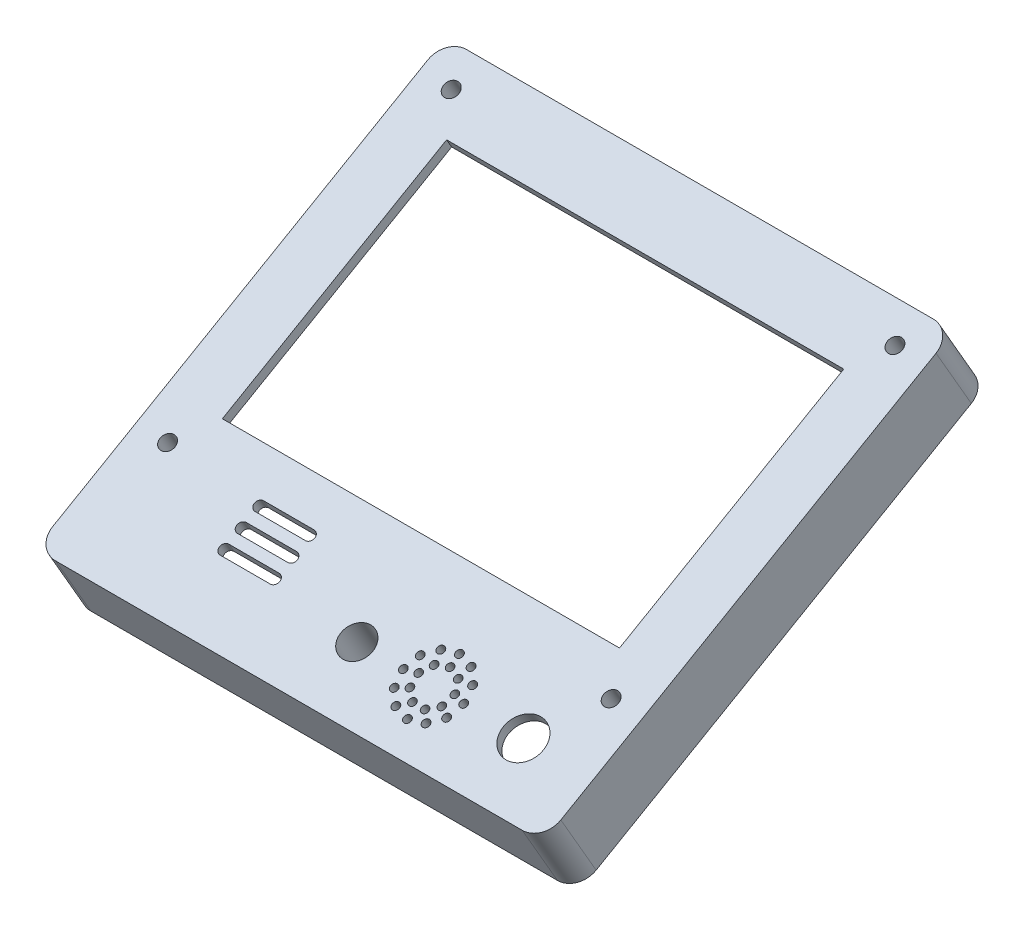
SolidWorks part; units mm, degrees
ref_plane "Front Plane" through (0, 0, 0) normal (0, 0, 1) x (1, 0, 0)
ref_plane "Top Plane" through (0, 0, 0) normal (0, 1, 0) x (1, 0, 0)
ref_plane "Right Plane" through (0, 0, 0) normal (1, 0, 0) x (0, 0, -1)
sketch "Sketch2" plane through (0, 0, 0) normal (0, 1, 0) x (1, 0, 0)
  line L0 (0, 0) -> (50081.3291, 0) construction
  line L1 (0, 0) -> (0, -110950.6715) construction
  line L2 (0, -89480) -> (38648.623, -89480) construction
  point P6 (25040.6645, 0)
  dimension "D1" = 89480
ref_plane "Plane3" through (0, 38745.9766, 22370) normal (0, 0.866, 0.5) x (1, 0, 0)
sketch "Sketch3" plane through (0, 38745.9766, 22370) normal (0, 0.866, 0.5) x (1, 0, 0)
  line L4 (-50374.8432, -6320.5279) -> (50376.1874, -6320.5279)
  line L5 (50376.1874, -6320.5279) -> (50376.1874, -100416.3212)
  line L6 (50376.1874, -100416.3212) -> (-50374.8432, -100416.3212)
  line L7 (-50374.8432, -100416.3212) -> (-50374.8432, -6320.5279)
  point P8 (-50374.8432, -6320.5279)
  point P9 (50376.1874, -6320.5279)
  point P10 (50376.1874, -100416.3212)
  point P11 (-50374.8432, -100416.3212)
sketch "Sketch4" plane through (0, 0, 0) normal (1, 0, 0) x (0, 0, -1)
  line L0 (0, 0) -> (-89485.0672, 0) construction
  line L1 (0, 0) -> (-110950.6715, 0) construction
  line L2 (-89485.0672, 0) -> (-89485.0672, -20894.7406) construction
extrude "Boss-Extrude1" add sketch "Sketch3" along normal blind 14000
shell "Shell1" thickness 2000 removed face at (0.6721, 12061.7643, 68588.4114)
sketch "Sketch5" plane through (0, 50870.3322, 29370) normal (0, 0.866, 0.5) x (1, 0, 0)
  line L0 (-24605.495, -77761.1574) -> (-14621.2598, -77761.1574)
  line L1 (-39129.4107, -70448.8565) -> (39606.8675, -70448.8565)
  line L2 (-39129.4107, -70448.8565) -> (-39129.4107, -19112.8031)
  line L3 (-39129.4107, -19112.8031) -> (39606.8675, -19112.8031)
  line L4 (39606.8675, -70448.8565) -> (39606.8675, -19112.8031)
  line L5 (-24605.495, -79737.168) -> (-14621.2598, -79737.168)
  line L6 (-24597.3605, -81751.7796) -> (-14620.8656, -81751.7796)
  line L7 (-24597.3605, -83766.3728) -> (-14620.8656, -83766.3728)
  line L8 (-24586.8841, -85741.4185) -> (-14643.555, -85741.4185)
  line L9 (-24586.8841, -87752.0657) -> (-14643.555, -87752.0657)
  circle A0 centre (-43988.643, -12447.8612) radius 1501.7923
  circle A1 centre (43969.8589, -12425.4966) radius 1493.6873
  circle A2 centre (43990.1719, -77427.1184) radius 1490.7249
  circle A3 centre (36420.679, -88766.8916) radius 3982.1728
  circle A4 centre (3383.4287, -88760.7991) radius 3170.6094
  circle A5 centre (-43960.9906, -77415.5626) radius 1490.364
  arc A6 (-24605.495, -77761.1574) -> (-24605.495, -79737.168) centre (-24605.495, -78749.1627) ccw
  arc A7 (-24597.3605, -81751.7796) -> (-24597.3605, -83766.3728) centre (-24597.3605, -82759.0762) ccw
  arc A8 (-24586.8841, -85741.4185) -> (-24586.8841, -87752.0657) centre (-24586.8841, -86746.7421) ccw
  arc A9 (-14643.555, -87752.0657) -> (-14643.555, -85741.4185) centre (-14643.555, -86746.7421) ccw
  arc A10 (-14620.8656, -83766.3728) -> (-14620.8656, -81751.7796) centre (-14620.8656, -82759.0762) ccw
  arc A11 (-14621.2598, -79737.168) -> (-14621.2598, -77761.1574) centre (-14621.2598, -78749.1627) ccw
  circle A13 centre (12622.7096, -88782.7367) radius 737.9119
  circle A14 centre (13435.1258, -91791.6852) radius 740.8686
  circle A15 centre (15520.9408, -90608.0936) radius 724.5909
  circle A16 centre (15113.5927, -88150.56) radius 724.1259
  circle A17 centre (16340.1747, -86021.6181) radius 734.9855
  circle A18 centre (18726.3962, -88814.2471) radius 3673.2587 construction
  circle A20 centre (18752.6437, -85141.0822) radius 724.1259
  circle A21 centre (21107.5678, -86017.3111) radius 724.1259
  circle A22 centre (22348.3153, -88202.2574) radius 724.1259
  circle A23 centre (21894.3266, -90673.5605) radius 724.1259
  circle A24 centre (19958.028, -92274.8702) radius 724.1259
  circle A25 centre (17445.4352, -92256.9159) radius 724.1259
  circle A27 centre (16385.438, -85983.568) radius 724.1259 [skipped]
  circle A28 centre (15532.2183, -90628.0986) radius 724.1259 [skipped]
  circle A29 centre (18599.5006, -88783.1535) radius 5976.7909 construction
  circle A31 centre (13411.8483, -85818.0355) radius 740.8686
  circle A32 centre (15589.8357, -83623.0077) radius 740.8686
  circle A33 centre (18573.5419, -82811.0517) radius 740.8686
  circle A34 centre (21563.4854, -83599.7302) radius 740.8686
  circle A35 centre (23758.5132, -85777.7176) radius 740.8686
  circle A36 centre (24570.4692, -88761.4239) radius 740.8686
  circle A37 centre (23781.7907, -91751.3674) radius 740.8686
  circle A38 centre (21603.8033, -93946.3951) radius 740.8686
  circle A39 centre (18620.097, -94758.3512) radius 740.8686
  circle A40 centre (15630.1535, -93969.6726) radius 740.8686
  circle A41 centre (12623.1697, -88807.9789) radius 740.8686 [skipped]
  point P60 (18726.3962, -88814.2471)
  point P86 (18596.8195, -88784.7014)
  dimension "D1" = 9
  dimension "D2" = 12
sketch "Sketch6" plane through (0, 38745.9766, 22370) normal (0, -0.866, -0.5) x (1, 0, 0)
  line L0 (50376.1874, 53368.4246) -> (48347.6296, 53368.4246)
  line L1 (50376.1874, 6320.5279) -> (50376.1874, 100416.3212) construction
  point P4 (48522.4407, 53368.4246)
  point P5 (48347.6296, 53368.4246)
extrude "Cut-Extrude1" cut sketch "Sketch5" against normal through all
sketch "Sketch7" plane through (0, 49138.2814, 28370) normal (0, -0.866, -0.5) x (1, 0, 0)
  circle A4 centre (43969.8589, 12425.4966) radius 3521.6824
  circle A5 centre (-43988.643, 12447.8612) radius 3521.6824
  circle A6 centre (-43960.9906, 77415.5626) radius 3500
  circle A7 centre (43990.1719, 77427.1184) radius 3521.6824
  circle A8 centre (3383.4287, 88760.7991) radius 4000
  dimension "D1" = 8000
  dimension "D2" = 7000
extrude "Boss-Extrude2" add sketch "Sketch7" along normal blind 6300
sketch "Sketch8" plane through (0, 49138.2814, 28370) normal (0, 0.866, 0.5) x (1, 0, 0)
  circle A0 centre (3383.4287, -88760.7991) radius 3170.6094
  circle A1 centre (-43960.9906, -77415.5626) radius 1490.364
  circle A2 centre (-43988.643, -12447.8612) radius 1501.7923
  circle A3 centre (43969.8589, -12425.4966) radius 1493.6873
  circle A4 centre (43990.1719, -77427.1184) radius 1490.7249
extrude "Cut-Extrude2" cut sketch "Sketch8" against normal through all
sketch "Sketch9" plane through (0, 38745.9766, 22370) normal (0, 0.866, 0.5) x (1, 0, 0)
  circle A0 centre (-46197.4506, -96238.9286) radius 4177.3926
fillet "Fillet1" radius 4100 4 edges at (-50374.8432, 41647.8904, 31343.7378) (50376.1874, 41647.8904, 31343.7378) (50376.1874, -5400.0062, 112833.0851) (-50374.8432, -5400.0062, 112833.0851)
